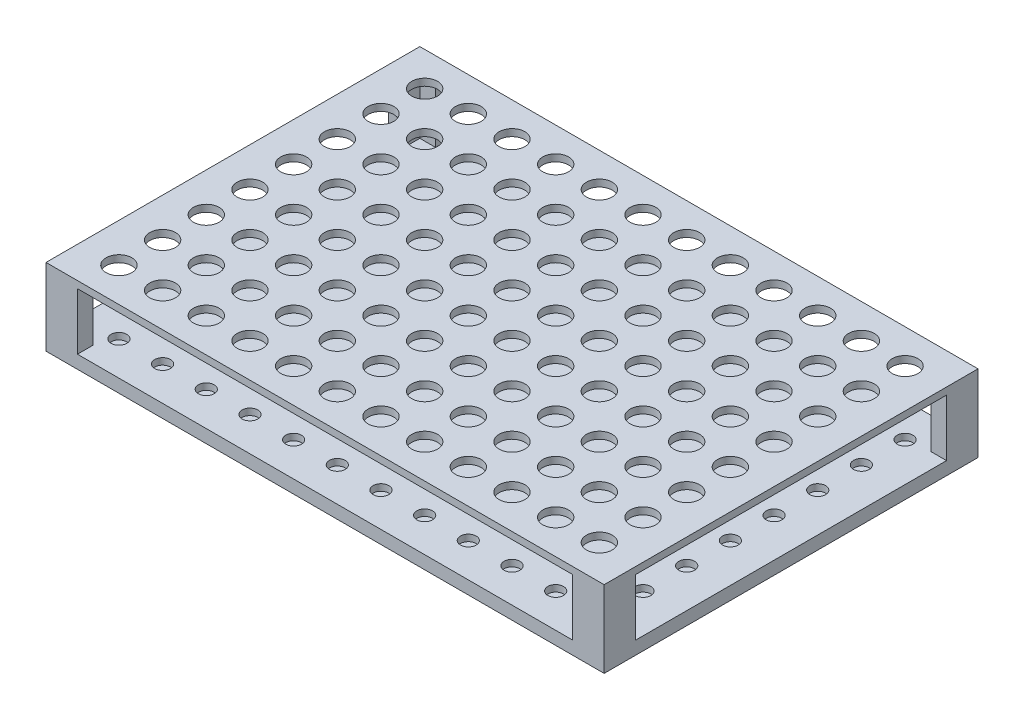
SolidWorks part; units mm, degrees
ref_plane "Front Plane" through (0, 0, 0) normal (0, 0, 1) x (1, 0, 0)
ref_plane "Top Plane" through (0, 0, 0) normal (0, 1, 0) x (1, 0, 0)
ref_plane "Right Plane" through (0, 0, 0) normal (1, 0, 0) x (0, 0, -1)
sketch "Sketch1" plane through (0, 0, 0) normal (0, 1, 0) x (1, 0, 0)
  line L1 (63.9, -42.8) -> (-63.9, -42.8)
  line L2 (63.9, -42.8) -> (63.9, 42.8)
  line L3 (63.9, 42.8) -> (-63.9, 42.8)
  line L4 (-63.9, -42.8) -> (-63.9, 42.8)
  line L5 (63.9, -42.8) -> (-63.9, 42.8) construction
  line L6 (63.9, 42.8) -> (-63.9, -42.8) construction
  point P0 (0, 0)
  dimension "D1" = 127.8
  dimension "D2" = 85.6
extrude "Boss-Extrude1" add sketch "Sketch1" along normal blind 3
sketch "Sketch2" plane through (0, 3, 0) normal (0, 1, 0) x (1, 0, 0)
  line L0 (-63.9, 42.8) -> (-56.7, 42.8)
  line L5 (63.9, 42.8) -> (-63.9, 42.8) construction
  line L6 (-56.7, 42.8) -> (-56.7, 39.2)
  line L7 (-56.7, 39.2) -> (-60.3, 39.2)
  line L8 (-60.3, 39.2) -> (-60.3, 35.6)
  line L9 (-60.3, 35.6) -> (-63.9, 35.6)
  line L10 (-63.9, 42.8) -> (-63.9, -42.8) construction
  line L11 (-63.9, 35.6) -> (-63.9, 42.8)
  line L12 (0, 42.8) -> (0, -42.8) construction
  line L13 (-63.9, -42.8) -> (63.9, -42.8) construction
  line L14 (-63.9, 0) -> (63.9, 0) construction
  line L15 (63.9, -42.8) -> (63.9, 42.8) construction
  line L16 (63.9, 35.6) -> (63.9, 42.8)
  line L17 (60.3, 35.6) -> (63.9, 35.6)
  line L18 (60.3, 39.2) -> (60.3, 35.6)
  line L19 (56.7, 39.2) -> (60.3, 39.2)
  line L20 (56.7, 42.8) -> (56.7, 39.2)
  line L21 (63.9, 42.8) -> (56.7, 42.8)
  line L22 (63.9, -42.8) -> (56.7, -42.8)
  line L23 (56.7, -42.8) -> (56.7, -39.2)
  line L24 (56.7, -39.2) -> (60.3, -39.2)
  line L25 (60.3, -39.2) -> (60.3, -35.6)
  line L26 (60.3, -35.6) -> (63.9, -35.6)
  line L27 (63.9, -35.6) -> (63.9, -42.8)
  line L28 (-63.9, -35.6) -> (-63.9, -42.8)
  line L29 (-60.3, -35.6) -> (-63.9, -35.6)
  line L30 (-60.3, -39.2) -> (-60.3, -35.6)
  line L31 (-56.7, -39.2) -> (-60.3, -39.2)
  line L32 (-56.7, -42.8) -> (-56.7, -39.2)
  line L33 (-63.9, -42.8) -> (-56.7, -42.8)
  dimension "D1" = 7.2
  dimension "D2" = 7.2
  dimension "D3" = 3.6
  dimension "D4" = 3.6
extrude "Boss-Extrude2" add sketch "Sketch2" along normal blind 13
ref_plane "Plane2" through (0, 16, 0) normal (0, 1, 0) x (1, 0, 0)
sketch "Sketch3" plane through (0, 16, 0) normal (0, 1, 0) x (1, 0, 0)
  line L1 (-63.9, 42.8) -> (63.9, 42.8)
  line L2 (-63.9, 42.8) -> (-63.9, -42.8)
  line L3 (-63.9, -42.8) -> (63.9, -42.8)
  line L4 (63.9, 42.8) -> (63.9, -42.8)
extrude "Boss-Extrude3" add sketch "Sketch3" along normal blind 1.6
ref_plane "Plane3" through (0, 17.6, 0) normal (0, 1, 0) x (1, 0, 0)
sketch "Sketch6" plane through (0, 17.6, 0) normal (0, 1, 0) x (1, 0, 0)
  line L1 (-63.9, 42.8) -> (-63.9, -42.8) construction
  line L6 (63.9, 42.8) -> (-63.9, 42.8) construction
  line L8 (0, 42.8) -> (0, -42.8) construction
  line L9 (-63.9, -42.8) -> (63.9, -42.8) construction
  circle A0 centre (-55, 35) radius 2.95
  circle A1 centre (-45, 35) radius 2.95
  circle A2 centre (-35, 35) radius 2.95
  circle A3 centre (-25, 35) radius 2.95
  circle A4 centre (-15, 35) radius 2.95
  circle A5 centre (-5, 35) radius 2.95
  circle A6 centre (5, 35) radius 2.95
  circle A7 centre (15, 35) radius 2.95
  circle A8 centre (25, 35) radius 2.95
  circle A9 centre (35, 35) radius 2.95
  circle A10 centre (45, 35) radius 2.95
  circle A11 centre (55, 35) radius 2.95
  circle A19 centre (-55, 25) radius 2.95
  circle A20 centre (-55, 15) radius 2.95
  circle A21 centre (-55, 5) radius 2.95
  circle A22 centre (-55, -5) radius 2.95
  circle A23 centre (-55, -15) radius 2.95
  circle A24 centre (-55, -25) radius 2.95
  circle A25 centre (-55, -35) radius 2.95
  circle A26 centre (-45, 25) radius 2.95
  circle A27 centre (-45, 15) radius 2.95
  circle A28 centre (-45, 5) radius 2.95
  circle A29 centre (-45, -5) radius 2.95
  circle A30 centre (-45, -15) radius 2.95
  circle A31 centre (-45, -25) radius 2.95
  circle A32 centre (-45, -35) radius 2.95
  circle A33 centre (-35, 25) radius 2.95
  circle A34 centre (-35, 15) radius 2.95
  circle A35 centre (-35, 5) radius 2.95
  circle A36 centre (-35, -5) radius 2.95
  circle A37 centre (-35, -15) radius 2.95
  circle A38 centre (-35, -25) radius 2.95
  circle A39 centre (-35, -35) radius 2.95
  circle A40 centre (-25, 25) radius 2.95
  circle A41 centre (-25, 15) radius 2.95
  circle A42 centre (-25, 5) radius 2.95
  circle A43 centre (-25, -5) radius 2.95
  circle A44 centre (-25, -15) radius 2.95
  circle A45 centre (-25, -25) radius 2.95
  circle A46 centre (-25, -35) radius 2.95
  circle A47 centre (-15, 25) radius 2.95
  circle A48 centre (-15, 15) radius 2.95
  circle A49 centre (-15, 5) radius 2.95
  circle A50 centre (-15, -5) radius 2.95
  circle A51 centre (-15, -15) radius 2.95
  circle A52 centre (-15, -25) radius 2.95
  circle A53 centre (-15, -35) radius 2.95
  circle A54 centre (-5, 25) radius 2.95
  circle A55 centre (-5, 15) radius 2.95
  circle A56 centre (-5, 5) radius 2.95
  circle A57 centre (-5, -5) radius 2.95
  circle A58 centre (-5, -15) radius 2.95
  circle A59 centre (-5, -25) radius 2.95
  circle A60 centre (-5, -35) radius 2.95
  circle A61 centre (5, 25) radius 2.95
  circle A62 centre (5, 15) radius 2.95
  circle A63 centre (5, 5) radius 2.95
  circle A64 centre (5, -5) radius 2.95
  circle A65 centre (5, -15) radius 2.95
  circle A66 centre (5, -25) radius 2.95
  circle A67 centre (5, -35) radius 2.95
  circle A68 centre (15, 25) radius 2.95
  circle A69 centre (15, 15) radius 2.95
  circle A70 centre (15, 5) radius 2.95
  circle A71 centre (15, -5) radius 2.95
  circle A72 centre (15, -15) radius 2.95
  circle A73 centre (15, -25) radius 2.95
  circle A74 centre (15, -35) radius 2.95
  circle A75 centre (25, 25) radius 2.95
  circle A76 centre (25, 15) radius 2.95
  circle A77 centre (25, 5) radius 2.95
  circle A78 centre (25, -5) radius 2.95
  circle A79 centre (25, -15) radius 2.95
  circle A80 centre (25, -25) radius 2.95
  circle A81 centre (25, -35) radius 2.95
  circle A82 centre (35, 25) radius 2.95
  circle A83 centre (35, 15) radius 2.95
  circle A84 centre (35, 5) radius 2.95
  circle A85 centre (35, -5) radius 2.95
  circle A86 centre (35, -15) radius 2.95
  circle A87 centre (35, -25) radius 2.95
  circle A88 centre (35, -35) radius 2.95
  circle A89 centre (45, 25) radius 2.95
  circle A90 centre (45, 15) radius 2.95
  circle A91 centre (45, 5) radius 2.95
  circle A92 centre (45, -5) radius 2.95
  circle A93 centre (45, -15) radius 2.95
  circle A94 centre (45, -25) radius 2.95
  circle A95 centre (45, -35) radius 2.95
  circle A96 centre (55, 25) radius 2.95
  circle A97 centre (55, 15) radius 2.95
  circle A98 centre (55, 5) radius 2.95
  circle A99 centre (55, -5) radius 2.95
  circle A100 centre (55, -15) radius 2.95
  circle A101 centre (55, -25) radius 2.95
  circle A102 centre (55, -35) radius 2.95
  dimension "D5" = 12
  dimension "D6" = 8.9
  dimension "D8" = 7.8
extrude "Cut-Extrude1" cut sketch "Sketch6" against normal blind 1.6
ref_plane "Plane4" through (0, 3, 0) normal (0, 1, 0) x (1, 0, 0)
sketch "Sketch8" plane through (0, 3, 0) normal (0, 1, 0) x (1, 0, 0)
  line L0 (-63.9, 35.6) -> (-63.9, -35.6) construction
  line L1 (56.7, 42.8) -> (-56.7, 42.8) construction
  circle A0 centre (-55, 35) radius 1.8
  circle A1 centre (-45, 35) radius 1.8
  circle A2 centre (-35, 35) radius 1.8
  circle A3 centre (-25, 35) radius 1.8
  circle A4 centre (-15, 35) radius 1.8
  circle A5 centre (-5, 35) radius 1.8
  circle A6 centre (5, 35) radius 1.8
  circle A7 centre (15, 35) radius 1.8
  circle A8 centre (25, 35) radius 1.8
  circle A9 centre (35, 35) radius 1.8
  circle A10 centre (45, 35) radius 1.8
  circle A11 centre (55, 35) radius 1.8
  circle A12 centre (-55, 25) radius 1.8
  circle A13 centre (-55, 15) radius 1.8
  circle A14 centre (-55, 5) radius 1.8
  circle A15 centre (-55, -5) radius 1.8
  circle A16 centre (-55, -15) radius 1.8
  circle A17 centre (-55, -25) radius 1.8
  circle A18 centre (-55, -35) radius 1.8
  circle A19 centre (-45, 25) radius 1.8
  circle A20 centre (-45, 15) radius 1.8
  circle A21 centre (-45, 5) radius 1.8
  circle A22 centre (-45, -5) radius 1.8
  circle A23 centre (-45, -15) radius 1.8
  circle A24 centre (-45, -25) radius 1.8
  circle A25 centre (-45, -35) radius 1.8
  circle A26 centre (-35, 25) radius 1.8
  circle A27 centre (-35, 15) radius 1.8
  circle A28 centre (-35, 5) radius 1.8
  circle A29 centre (-35, -5) radius 1.8
  circle A30 centre (-35, -15) radius 1.8
  circle A31 centre (-35, -25) radius 1.8
  circle A32 centre (-35, -35) radius 1.8
  circle A33 centre (-25, 25) radius 1.8
  circle A34 centre (-25, 15) radius 1.8
  circle A35 centre (-25, 5) radius 1.8
  circle A36 centre (-25, -5) radius 1.8
  circle A37 centre (-25, -15) radius 1.8
  circle A38 centre (-25, -25) radius 1.8
  circle A39 centre (-25, -35) radius 1.8
  circle A40 centre (-15, 25) radius 1.8
  circle A41 centre (-15, 15) radius 1.8
  circle A42 centre (-15, 5) radius 1.8
  circle A43 centre (-15, -5) radius 1.8
  circle A44 centre (-15, -15) radius 1.8
  circle A45 centre (-15, -25) radius 1.8
  circle A46 centre (-15, -35) radius 1.8
  circle A47 centre (-5, 25) radius 1.8
  circle A48 centre (-5, 15) radius 1.8
  circle A49 centre (-5, 5) radius 1.8
  circle A50 centre (-5, -5) radius 1.8
  circle A51 centre (-5, -15) radius 1.8
  circle A52 centre (-5, -25) radius 1.8
  circle A53 centre (-5, -35) radius 1.8
  circle A54 centre (5, 25) radius 1.8
  circle A55 centre (5, 15) radius 1.8
  circle A56 centre (5, 5) radius 1.8
  circle A57 centre (5, -5) radius 1.8
  circle A58 centre (5, -15) radius 1.8
  circle A59 centre (5, -25) radius 1.8
  circle A60 centre (5, -35) radius 1.8
  circle A61 centre (15, 25) radius 1.8
  circle A62 centre (15, 15) radius 1.8
  circle A63 centre (15, 5) radius 1.8
  circle A64 centre (15, -5) radius 1.8
  circle A65 centre (15, -15) radius 1.8
  circle A66 centre (15, -25) radius 1.8
  circle A67 centre (15, -35) radius 1.8
  circle A68 centre (25, 25) radius 1.8
  circle A69 centre (25, 15) radius 1.8
  circle A70 centre (25, 5) radius 1.8
  circle A71 centre (25, -5) radius 1.8
  circle A72 centre (25, -15) radius 1.8
  circle A73 centre (25, -25) radius 1.8
  circle A74 centre (25, -35) radius 1.8
  circle A75 centre (35, 25) radius 1.8
  circle A76 centre (35, 15) radius 1.8
  circle A77 centre (35, 5) radius 1.8
  circle A78 centre (35, -5) radius 1.8
  circle A79 centre (35, -15) radius 1.8
  circle A80 centre (35, -25) radius 1.8
  circle A81 centre (35, -35) radius 1.8
  circle A82 centre (45, 25) radius 1.8
  circle A83 centre (45, 15) radius 1.8
  circle A84 centre (45, 5) radius 1.8
  circle A85 centre (45, -5) radius 1.8
  circle A86 centre (45, -15) radius 1.8
  circle A87 centre (45, -25) radius 1.8
  circle A88 centre (45, -35) radius 1.8
  circle A89 centre (55, 25) radius 1.8
  circle A90 centre (55, 15) radius 1.8
  circle A91 centre (55, 5) radius 1.8
  circle A92 centre (55, -5) radius 1.8
  circle A93 centre (55, -15) radius 1.8
  circle A94 centre (55, -25) radius 1.8
  circle A95 centre (55, -35) radius 1.8
  dimension "D1" = 8.9
  dimension "D2" = 7.8
  dimension "D3" = 12
extrude "Cut-Extrude2" cut sketch "Sketch8" against normal blind 1.5
